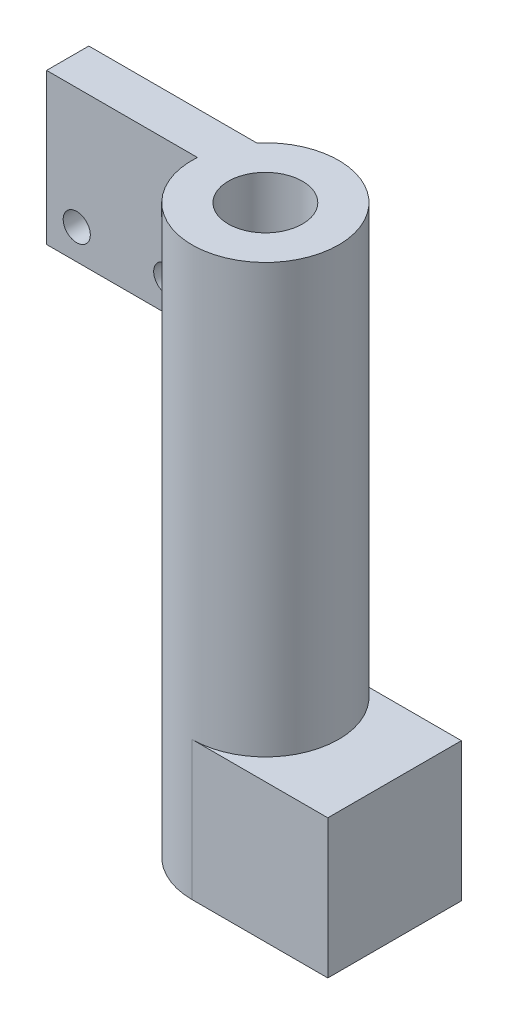
SolidWorks part; units mm, degrees
ref_plane "Front Plane" through (0, 0, 0) normal (0, 0, 1) x (1, 0, 0)
ref_plane "Top Plane" through (0, 0, 0) normal (0, 1, 0) x (1, 0, 0)
ref_plane "Right Plane" through (0, 0, 0) normal (1, 0, 0) x (0, 0, -1)
sketch "Sketch1" plane through (0, 0, 0) normal (0, 1, 0) x (1, 0, 0)
  circle A0 centre (0, 0) radius 6.15
  dimension "D1" = 12.3
extrude "Extrude-Thin1" add sketch "Sketch1" along normal blind 94 thin thin type one direction wall 6
sketch "Sketch2" plane through (0, 94, 0) normal (0, 1, 0) x (1, 0, 0)
  line L0 (-12.1202, 0.85) -> (-37.1202, 0.85)
  line L1 (-37.1202, 0.85) -> (-37.1202, 7.85)
  line L2 (-37.1202, 7.85) -> (-9.2736, 7.85)
  line L3 (0, -12.15) -> (5, -12.15) construction
  circle A0 centre (0, 0) radius 12.15 construction
  arc A1 (-9.2736, 7.85) -> (-12.1202, 0.85) centre (0, 0) ccw
  dimension "D1" = 7
  dimension "D2" = 25
  dimension "D3" = 5
  dimension "D4" = 13
extrude "limit switch mount" add sketch "Sketch2" against normal blind 25
sketch "Sketch3" plane through (0, 0, -0.85) normal (0, 0, 1) x (1, 0, 0)
  line L0 (-37.1202, 69) -> (-12.1202, 69) construction
  line L1 (-37.1202, 69) -> (-37.1202, 94) construction
  circle A0 centre (-17.1202, 74) radius 2.25
  circle A1 centre (-32.1202, 74) radius 2.25
  dimension "D1" = 4.5
  dimension "D2" = 5
  dimension "D3" = 15
  dimension "D4" = 5
extrude "heat set inserts" cut sketch "Sketch3" against normal up to surface (7 mm away) up to face at (-23.1969, 81.5, -7.85)
sketch "Sketch4" plane through (0, 0, 0) normal (0, 0, 1) x (1, 0, 0)
  line L1 (0, 0) -> (22.5, 0)
  line L2 (0, 0) -> (0, 23)
  line L3 (0, 23) -> (22.5, 23)
  line L4 (22.5, 0) -> (22.5, 23)
  dimension "D1" = 22.5
  dimension "D2" = 23
extrude "Boss-Extrude1" add sketch "Sketch4" along normal blind 12.15 and the other way blind 10
extrude "Cut-Extrude1" cut sketch "Sketch1<3>" along normal up to surface (94 mm away) up to face at (-18.4206, 94, -2.1183)
sketch "Sketch1<3>" plane through (0, 0, 0) normal (0, 1, 0) x (1, 0, 0) same geometry as "Sketch1"
